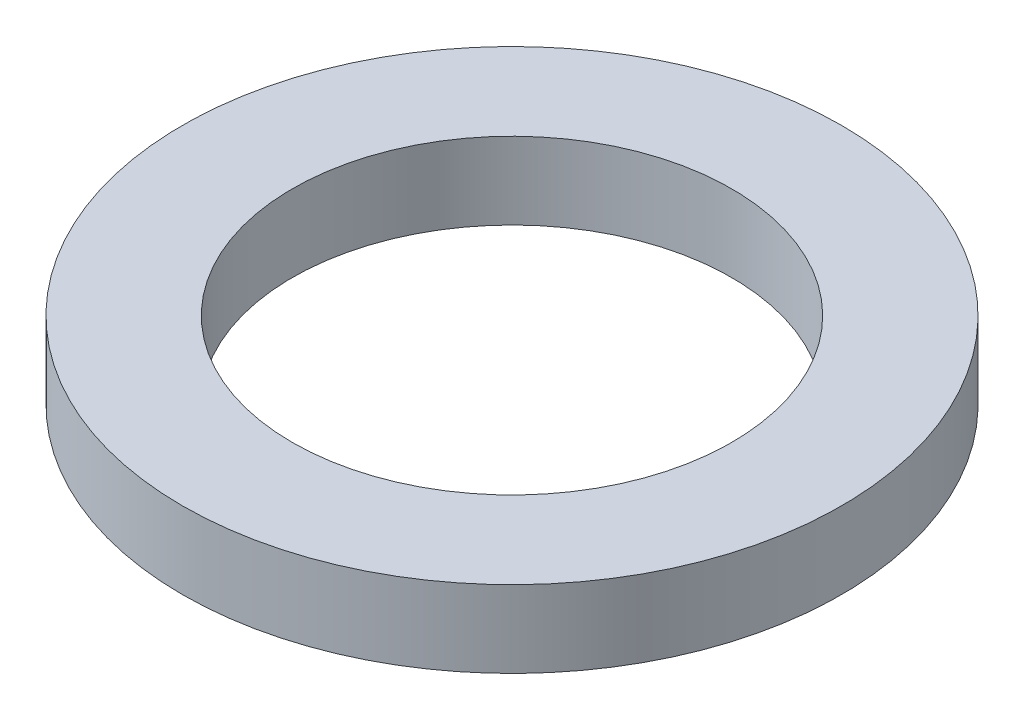
SolidWorks part; units mm, degrees
ref_plane "Front Plane" through (0, 0, 0) normal (0, 0, 1) x (1, 0, 0)
ref_plane "Top Plane" through (0, 0, 0) normal (0, 1, 0) x (1, 0, 0)
ref_plane "Right Plane" through (0, 0, 0) normal (1, 0, 0) x (0, 0, -1)
sketch "Sketch1" plane through (0, 0, 0) normal (0, 1, 0) x (1, 0, 0)
  circle A0 centre (0, 0) radius 30
  dimension "FLANGE_OD" = 60
extrude "Boss-Extrude1" add sketch "Sketch1" along normal blind 7
sketch "Sketch2" plane through (0, 0, 0) normal (0, 1, 0) x (1, 0, 0)
  circle A0 centre (0, 0) radius 20
  dimension "BORE_D" = 40
extrude "Cut-Extrude1" cut sketch "Sketch2" along normal through all
sketch "Sketch3" plane through (0, 7, 0) normal (0, 1, 0) x (1, 0, 0)
  circle A0 centre (0, 0) radius 13.2947 construction
  circle A1 centre (-13.2947, 0) radius 1.7814
  dimension "BOLT_D" = 3.5629
  dimension "BOLT_PCD" = 26.5894
extrude "Cut-Extrude2" cut sketch "Sketch3" against normal blind 5.587 rebuild error yes
pattern_circular "CirPattern1" count 6 over 360 rebuild error yes
